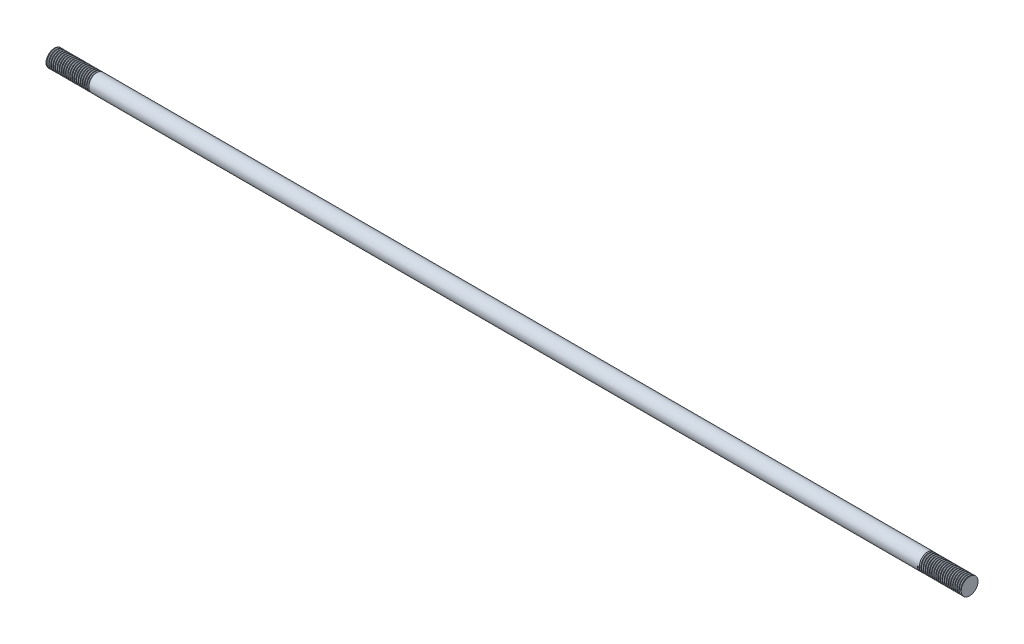
SolidWorks part; units mm, degrees
material "Alloy Steel"
ref_plane "Front Plane" through (0, 0, 0) normal (0, 0, 1) x (1, 0, 0)
ref_plane "Top Plane" through (0, 0, 0) normal (0, 1, 0) x (1, 0, 0)
ref_plane "Right Plane" through (0, 0, 0) normal (1, 0, 0) x (0, 0, -1)
sketch "Sketch1" plane through (0, 0, 0) normal (1, 0, 0) x (0, 0, -1)
  circle A0 centre (0, 0) radius 8
  dimension "D1" = 16
extrude "Boss-Extrude1" add sketch "Sketch1" along normal mid plane 870
thread "Thread1" pitch 2 method cut profile "Thread Profile1" start angle 0, offset 0, length 40, pitch 2, diameter 16
ref_plane "Plane1" through (-435, 0, -8) normal (0, -1, 0) x (0, 0, -1)
sketch "Thread Profile1" plane through (-435, 0, -8) normal (0, -1, 0) x (0, 0, -1)
  line L0 (0, 0) -> (0, 2) construction
  line L11 (0, 0) -> (0, 1.75)
  line L12 (0, 1.75) -> (-1.0825, 1.125)
  line L13 (-1.0825, 1.125) -> (-1.0825, 0.625)
  line L15 (-1.0825, 0.625) -> (0, 0)
  line L17 (-1.0825, 0.875) -> (0, 0.875) construction
  point P2 (0, 0)
  dimension "Pitch" = 2
  dimension "Profile_Angle" = 60
  dimension "Profile_Land" = 0.5
  dimension "Profile_Height" = 1.0825
thread "Thread2" pitch 2 method cut profile "Thread Profile2" start angle 0, offset 0, length 40, pitch 2, diameter 16
ref_plane "Plane2" through (435, 0, 8) normal (0, -1, 0) x (0, 0, 1)
sketch "Thread Profile2" plane through (435, 0, 8) normal (0, -1, 0) x (0, 0, 1)
  line L0 (0, 0) -> (0, 2) construction
  line L11 (0, 0) -> (0, 1.75)
  line L12 (0, 1.75) -> (-1.0825, 1.125)
  line L13 (-1.0825, 1.125) -> (-1.0825, 0.625)
  line L15 (-1.0825, 0.625) -> (0, 0)
  line L17 (-1.0825, 0.875) -> (0, 0.875) construction
  point P2 (0, 0)
  dimension "Pitch" = 2
  dimension "Profile_Angle" = 60
  dimension "Profile_Land" = 0.5
  dimension "Profile_Height" = 1.0825
